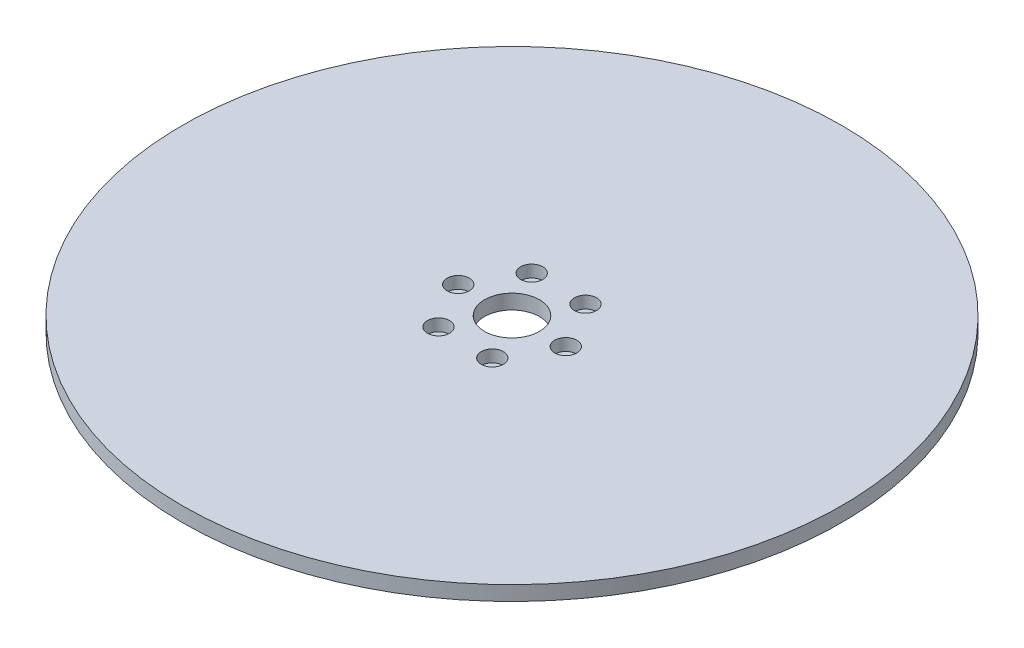
SolidWorks part; units mm, degrees
ref_plane "Front Plane" through (0, 0, 0) normal (0, 0, 1) x (1, 0, 0)
ref_plane "Top Plane" through (0, 0, 0) normal (0, 1, 0) x (1, 0, 0)
ref_plane "Right Plane" through (0, 0, 0) normal (1, 0, 0) x (0, 0, -1)
sketch "Sketch1" plane through (0, 0, 0) normal (0, 1, 0) x (1, 0, 0)
  circle A0 centre (0, 0) radius 90
  dimension "FLANGE_OD" = 180
extrude "Boss-Extrude1" add sketch "Sketch1" along normal blind 4
sketch "Sketch2" plane through (0, 0, 0) normal (0, 1, 0) x (1, 0, 0)
  circle A0 centre (0, 0) radius 7.5
  dimension "BORE_D" = 15
extrude "Cut-Extrude1" cut sketch "Sketch2" along normal through all
sketch "Sketch3" plane through (0, 4, 0) normal (0, 1, 0) x (1, 0, 0)
  circle A0 centre (0, 0) radius 14.6896 construction
  circle A1 centre (-14.6896, 0) radius 3.0238
  dimension "BOLT_D" = 6.0475
  dimension "BOLT_PCD" = 29.3792
extrude "Cut-Extrude2" cut sketch "Sketch3" against normal blind 3.297
pattern_circular "CirPattern1" count 6 over 360 about axis through (0, 0, 0) along (0, 1, 0) of "Cut-Extrude2"
